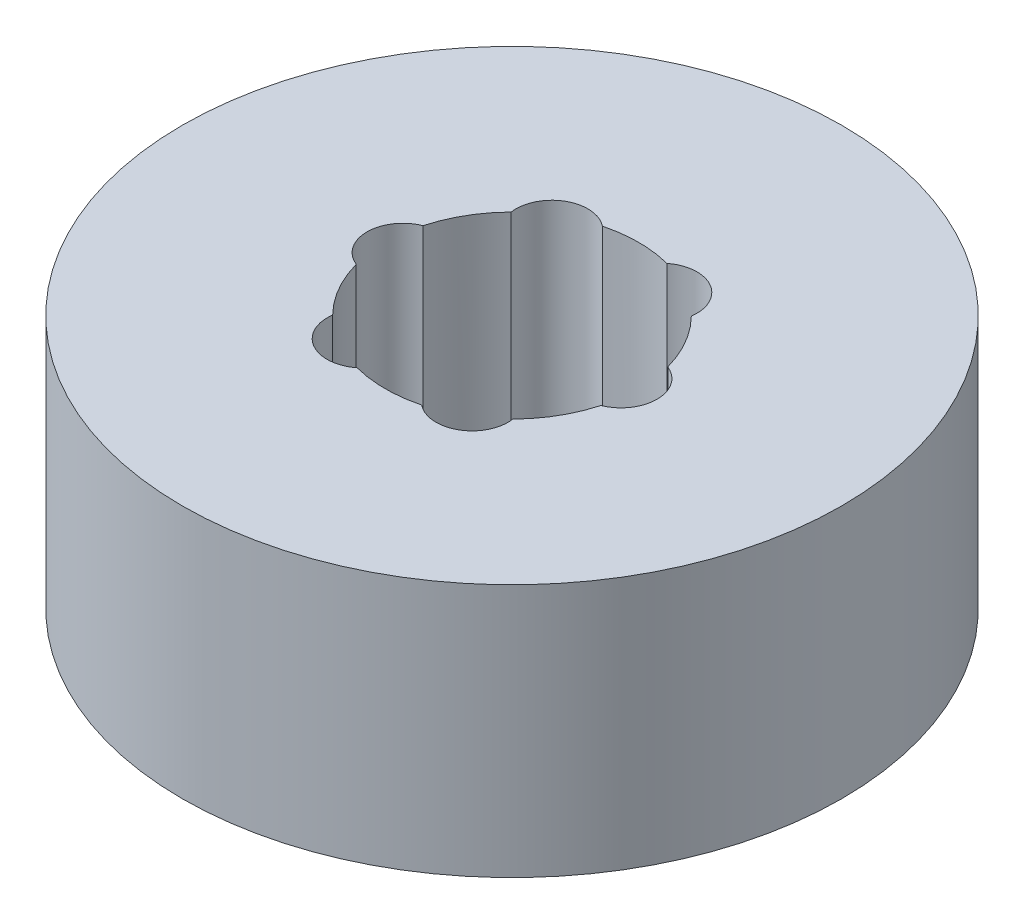
SolidWorks part; units mm, degrees
ref_plane "Front Plane" through (0, 0, 0) normal (0, 0, 1) x (1, 0, 0)
ref_plane "Top Plane" through (0, 0, 0) normal (0, 1, 0) x (1, 0, 0)
ref_plane "Right Plane" through (0, 0, 0) normal (1, 0, 0) x (0, 0, -1)
sketch "Sketch1" plane through (0, 0, 0) normal (0, 1, 0) x (1, 0, 0)
  circle A0 centre (0, 0) radius 32.5
  dimension "FLANGE_OD" = 65
extrude "Boss-Extrude1" add sketch "Sketch1" along normal blind 25
sketch "Sketch2" plane through (0, 0, 0) normal (0, 1, 0) x (1, 0, 0)
  circle A0 centre (0, 0) radius 12.5
  dimension "BORE_D" = 25
extrude "Cut-Extrude1" cut sketch "Sketch2" along normal through all
sketch "Sketch3" plane through (0, 25, 0) normal (0, 1, 0) x (1, 0, 0)
  circle A0 centre (0, 0) radius 10.7498 construction
  circle A1 centre (-10.7498, 0) radius 3.5455
  dimension "BOLT_D" = 7.0909
  dimension "BOLT_PCD" = 21.4996
extrude "Cut-Extrude2" cut sketch "Sketch3" against normal blind 19.2072
pattern_circular "CirPattern1" count 6 over 360 about axis through (0, 0, 0) along (0, 1, 0) of "Cut-Extrude2"
